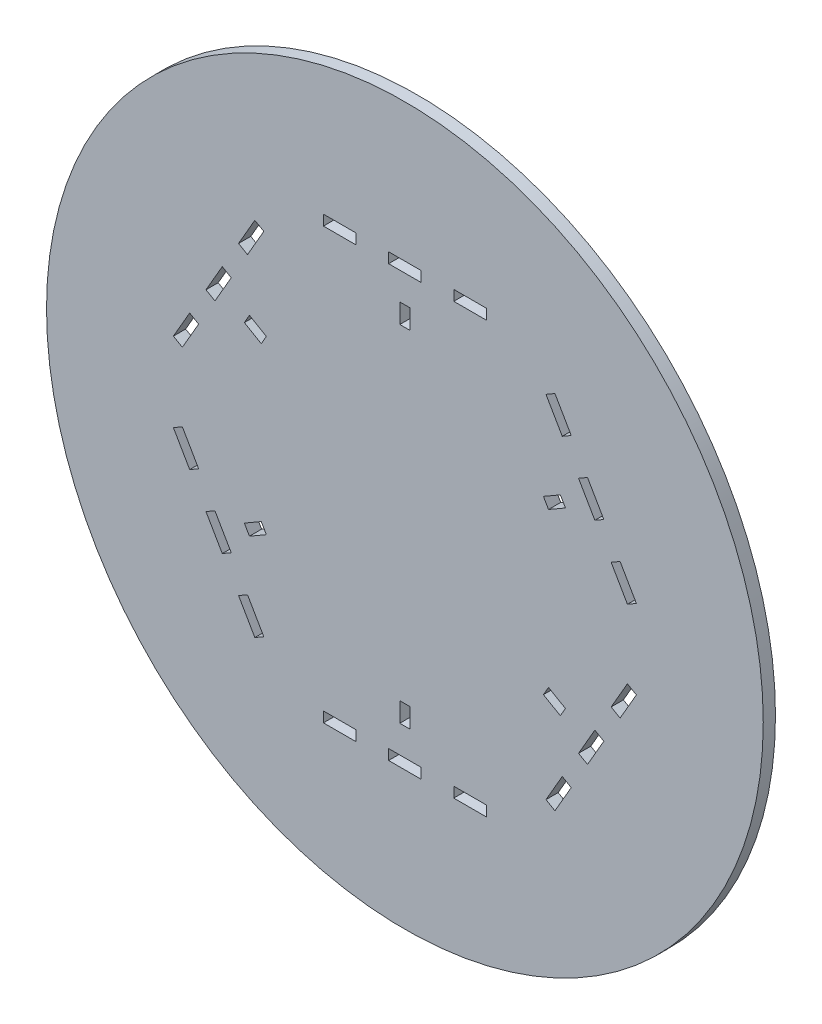
SolidWorks part; units mm, degrees
ref_plane "Front Plane" through (0, 0, 0) normal (0, 0, 1) x (1, 0, 0)
ref_plane "Top Plane" through (0, 0, 0) normal (0, 1, 0) x (1, 0, 0)
ref_plane "Right Plane" through (0, 0, 0) normal (1, 0, 0) x (0, 0, -1)
sketch "Sketch1" plane through (0, 0, 0) normal (0, 0, 1) x (1, 0, 0)
  line L0 (5, 67.6125) -> (-5, 67.6125)
  line L1 (-5, 67.6125) -> (-5, 64.4375)
  line L2 (-5, 64.4375) -> (5, 64.4375)
  line L3 (-15, 67.6125) -> (-5, 67.6125) construction
  line L4 (-15, 67.6125) -> (-25, 67.6125)
  line L5 (-15, 67.6125) -> (-15, 64.4375)
  line L6 (-15, 64.4375) -> (-25, 64.4375)
  line L7 (-25, 67.6125) -> (-25, 64.4375)
  line L8 (25, 67.6125) -> (25, 64.4375)
  line L9 (15, 64.4375) -> (25, 64.4375)
  line L10 (15, 67.6125) -> (15, 64.4375)
  line L11 (15, 67.6125) -> (25, 67.6125)
  line L12 (15, 67.6125) -> (5, 67.6125) construction
  line L13 (5, 67.6125) -> (5, 64.4375)
  line L14 (1.5625, 56) -> (-1.5625, 56)
  line L15 (-1.5625, 56) -> (-1.5625, 50)
  line L16 (-1.5625, 50) -> (1.5625, 50)
  line L17 (1.5625, 56) -> (1.5625, 50)
  line L18 (0, 64.4375) -> (0, 56) construction
  line L19 (0, 50) -> (0, 0) construction
  line L20 (61.0541, 29.4761) -> (56.0541, 38.1364)
  line L21 (56.0541, 38.1364) -> (53.3045, 36.5489)
  line L22 (53.3045, 36.5489) -> (58.3045, 27.8886)
  line L23 (51.0541, 46.7966) -> (46.0541, 55.4569)
  line L24 (51.0541, 46.7966) -> (48.3045, 45.2091)
  line L25 (48.3045, 45.2091) -> (43.3045, 53.8694)
  line L26 (46.0541, 55.4569) -> (43.3045, 53.8694)
  line L27 (71.0541, 12.1556) -> (68.3045, 10.5681)
  line L28 (63.3045, 19.2284) -> (68.3045, 10.5681)
  line L29 (66.0541, 20.8159) -> (63.3045, 19.2284)
  line L30 (66.0541, 20.8159) -> (71.0541, 12.1556)
  line L31 (61.0541, 29.4761) -> (58.3045, 27.8886)
  line L32 (49.2787, 26.6468) -> (47.7162, 29.3532)
  line L33 (47.7162, 29.3532) -> (42.52, 26.3532)
  line L34 (42.52, 26.3532) -> (44.0825, 23.6468)
  line L35 (49.2787, 26.6468) -> (44.0825, 23.6468)
  line L36 (51.0541, 46.7966) -> (56.0541, 38.1364) construction
  line L37 (66.0541, 20.8159) -> (61.0541, 29.4761) construction
  line L38 (55.8045, 32.2188) -> (48.4974, 28) construction
  line L39 (56.0541, -38.1364) -> (61.0541, -29.4761)
  line L40 (61.0541, -29.4761) -> (58.3045, -27.8886)
  line L41 (58.3045, -27.8886) -> (53.3045, -36.5489)
  line L42 (66.0541, -20.8159) -> (71.0541, -12.1556)
  line L43 (66.0541, -20.8159) -> (63.3045, -19.2284)
  line L44 (63.3045, -19.2284) -> (68.3045, -10.5681)
  line L45 (71.0541, -12.1556) -> (68.3045, -10.5681)
  line L46 (46.0541, -55.4569) -> (43.3045, -53.8694)
  line L47 (48.3045, -45.2091) -> (43.3045, -53.8694)
  line L48 (51.0541, -46.7966) -> (48.3045, -45.2091)
  line L49 (51.0541, -46.7966) -> (46.0541, -55.4569)
  line L50 (56.0541, -38.1364) -> (53.3045, -36.5489)
  line L51 (47.7162, -29.3532) -> (49.2787, -26.6468)
  line L52 (49.2787, -26.6468) -> (44.0825, -23.6468)
  line L53 (44.0825, -23.6468) -> (42.52, -26.3532)
  line L54 (47.7162, -29.3532) -> (42.52, -26.3532)
  line L55 (66.0541, -20.8159) -> (61.0541, -29.4761) construction
  line L56 (51.0541, -46.7966) -> (56.0541, -38.1364) construction
  line L57 (55.8045, -32.2187) -> (48.4974, -28) construction
  line L58 (-5, -67.6125) -> (5, -67.6125)
  line L59 (5, -67.6125) -> (5, -64.4375)
  line L60 (5, -64.4375) -> (-5, -64.4375)
  line L61 (15, -67.6125) -> (25, -67.6125)
  line L62 (15, -67.6125) -> (15, -64.4375)
  line L63 (15, -64.4375) -> (25, -64.4375)
  line L64 (25, -67.6125) -> (25, -64.4375)
  line L65 (-25, -67.6125) -> (-25, -64.4375)
  line L66 (-15, -64.4375) -> (-25, -64.4375)
  line L67 (-15, -67.6125) -> (-15, -64.4375)
  line L68 (-15, -67.6125) -> (-25, -67.6125)
  line L69 (-5, -67.6125) -> (-5, -64.4375)
  line L70 (-1.5625, -56) -> (1.5625, -56)
  line L71 (1.5625, -56) -> (1.5625, -50)
  line L72 (1.5625, -50) -> (-1.5625, -50)
  line L73 (-1.5625, -56) -> (-1.5625, -50)
  line L74 (15, -67.6125) -> (5, -67.6125) construction
  line L75 (-15, -67.6125) -> (-5, -67.6125) construction
  line L76 (0, -64.4375) -> (0, -56) construction
  line L77 (-61.0541, -29.4761) -> (-56.0541, -38.1364)
  line L78 (-56.0541, -38.1364) -> (-53.3045, -36.5489)
  line L79 (-53.3045, -36.5489) -> (-58.3045, -27.8886)
  line L80 (-51.0541, -46.7966) -> (-46.0541, -55.4569)
  line L81 (-51.0541, -46.7966) -> (-48.3045, -45.2091)
  line L82 (-48.3045, -45.2091) -> (-43.3045, -53.8694)
  line L83 (-46.0541, -55.4569) -> (-43.3045, -53.8694)
  line L84 (-71.0541, -12.1556) -> (-68.3045, -10.5681)
  line L85 (-63.3045, -19.2284) -> (-68.3045, -10.5681)
  line L86 (-66.0541, -20.8159) -> (-63.3045, -19.2284)
  line L87 (-66.0541, -20.8159) -> (-71.0541, -12.1556)
  line L88 (-61.0541, -29.4761) -> (-58.3045, -27.8886)
  line L89 (-49.2787, -26.6468) -> (-47.7162, -29.3532)
  line L90 (-47.7162, -29.3532) -> (-42.52, -26.3532)
  line L91 (-42.52, -26.3532) -> (-44.0825, -23.6468)
  line L92 (-49.2787, -26.6468) -> (-44.0825, -23.6468)
  line L93 (-51.0541, -46.7966) -> (-56.0541, -38.1364) construction
  line L94 (-66.0541, -20.8159) -> (-61.0541, -29.4761) construction
  line L95 (-55.8045, -32.2188) -> (-48.4974, -28) construction
  line L96 (-56.0541, 38.1364) -> (-61.0541, 29.4761)
  line L97 (-61.0541, 29.4761) -> (-58.3045, 27.8886)
  line L98 (-58.3045, 27.8886) -> (-53.3045, 36.5489)
  line L99 (-66.0541, 20.8159) -> (-71.0541, 12.1556)
  line L100 (-66.0541, 20.8159) -> (-63.3045, 19.2284)
  line L101 (-63.3045, 19.2284) -> (-68.3045, 10.5681)
  line L102 (-71.0541, 12.1556) -> (-68.3045, 10.5681)
  line L103 (-46.0541, 55.4569) -> (-43.3045, 53.8694)
  line L104 (-48.3045, 45.2091) -> (-43.3045, 53.8694)
  line L105 (-51.0541, 46.7966) -> (-48.3045, 45.2091)
  line L106 (-51.0541, 46.7966) -> (-46.0541, 55.4569)
  line L107 (-56.0541, 38.1364) -> (-53.3045, 36.5489)
  line L108 (-47.7162, 29.3532) -> (-49.2787, 26.6468)
  line L109 (-49.2787, 26.6468) -> (-44.0825, 23.6468)
  line L110 (-44.0825, 23.6468) -> (-42.52, 26.3532)
  line L111 (-47.7162, 29.3532) -> (-42.52, 26.3532)
  line L112 (-66.0541, 20.8159) -> (-61.0541, 29.4761) construction
  line L113 (-51.0541, 46.7966) -> (-56.0541, 38.1364) construction
  line L114 (-55.8045, 32.2188) -> (-48.4974, 28) construction
  circle A0 centre (0, 0) radius 110
  point P3 (0, 67.6125)
  point P13 (0, 64.4375)
  point P18 (0, 50)
  point P19 (0, 56)
  point P31 (58.5541, 33.8062)
  point P41 (55.8045, 32.2188)
  point P46 (43.3013, 25)
  point P47 (48.4974, 28)
  point P53 (58.5541, -33.8063)
  point P63 (55.8045, -32.2187)
  point P68 (43.3013, -25)
  point P69 (48.4974, -28)
  point P75 (0, -67.6125)
  point P85 (0, -64.4375)
  point P90 (0, -50)
  point P91 (0, -56)
  point P97 (-58.5541, -33.8063)
  point P107 (-55.8045, -32.2188)
  point P112 (-43.3013, -25)
  point P113 (-48.4974, -28)
  point P119 (-58.5541, 33.8063)
  point P129 (-55.8045, 32.2188)
  point P134 (-43.3013, 25)
  point P135 (-48.4974, 28)
  point P138 (0, 0)
  dimension "D8" = 220
  dimension "D1" = 3.175
  dimension "D2" = 10
  dimension "D3" = 1.5625
  dimension "D4" = 6
  dimension "D5" = 8.4375
  dimension "D6" = 50
  dimension "D7" = 6
extrude "Boss-Extrude1" add sketch "Sketch1" along normal mid plane 3.75
